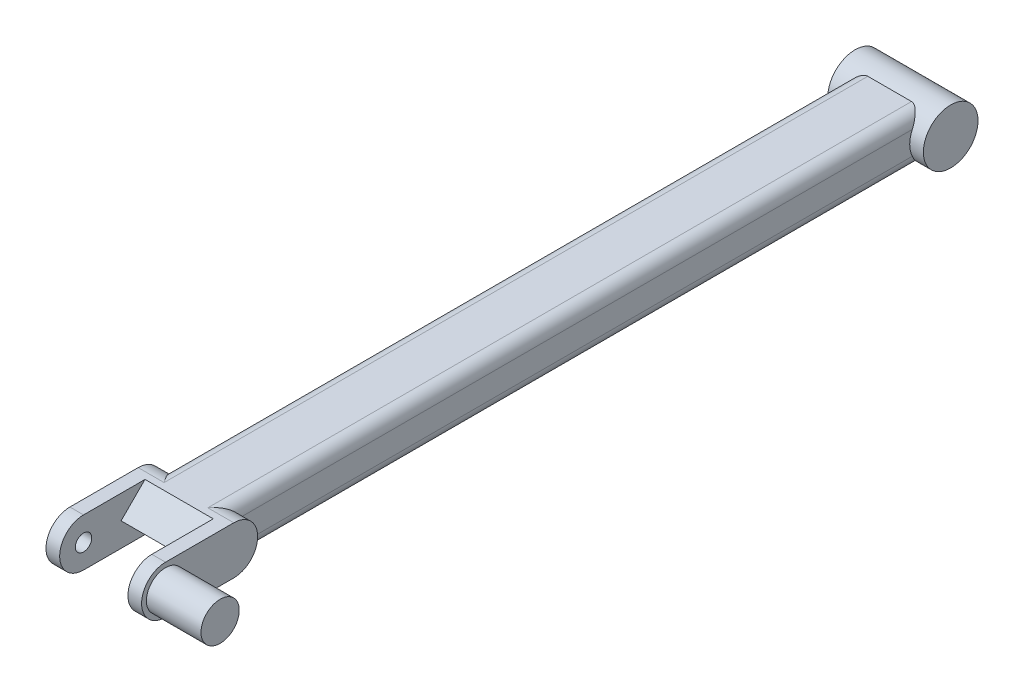
SolidWorks part; units mm, degrees
ref_plane "Ebene vorne" through (0, 0, 0) normal (0, 0, 1) x (1, 0, 0)
ref_plane "Ebene oben" through (0, 0, 0) normal (0, 1, 0) x (1, 0, 0)
ref_plane "Ebene rechts" through (0, 0, 0) normal (1, 0, 0) x (0, 0, -1)
sketch "Skizze1" plane through (0, 0, 0) normal (1, 0, 0) x (0, 0, -1)
  circle A0 centre (0, 0) radius 20
extrude "Aufsatz-Linear austragen1" add sketch "Skizze1" along normal blind 35 and the other way blind 35
sketch "Skizze2" plane through (0, 0, 0) normal (0, 0, 1) x (1, 0, 0)
  line L1 (-25, 17.5) -> (25, 17.5)
  line L2 (-25, 17.5) -> (-25, -17.5)
  line L3 (-25, -17.5) -> (25, -17.5)
  line L4 (25, 17.5) -> (25, -17.5)
  point P4 (-25, 0)
  point P6 (0, 17.5)
  dimension "D1" = 50
  dimension "D2" = 35
extrude "Aufsatz-Linear austragen2" add sketch "Skizze2" along normal blind 550
sketch "Skizze3" plane through (-25, 0, 0) normal (-1, 0, 0) x (0, 0, 1)
  line L0 (550, 17.5) -> (525, 17.5)
  line L1 (550, 17.5) -> (9.6825, 17.5) construction
  line L2 (550, -17.5) -> (525, -17.5)
  line L3 (550, -17.5) -> (9.6825, -17.5) construction
  line L4 (550, 17.5) -> (575, 17.5)
  line L5 (550, -17.5) -> (575, -17.5)
  arc A0 (525, 17.5) -> (525, -17.5) centre (525, 0) ccw
  arc A1 (575, 17.5) -> (575, -17.5) centre (575, 0) cw
  dimension "D1" = 25
  dimension "D2" = 25
extrude "Aufsatz-Linear austragen3" add sketch "Skizze3" along normal blind 10
sketch "Skizze4" plane through (-35, 0, 0) normal (-1, 0, 0) x (0, 0, 1)
  line L0 (575, 17.5) -> (525, 17.5) construction
  circle A0 centre (575, 0) radius 6
  point P4 (550, 17.5)
  dimension "D1" = 25
extrude "Schnitt-Linear austragen1" cut sketch "Skizze4" against normal up to next
mirror "Spiegeln1" about plane through (0, 0, 0) normal (1, 0, 0) of "Aufsatz-Linear austragen3", "Schnitt-Linear austragen1"
sketch "Skizze5" plane through (35, 0, 0) normal (1, 0, 0) x (0, 0, -1)
  circle A0 centre (-575, 0) radius 14
extrude "Aufsatz-Linear austragen4" add sketch "Skizze5" along normal blind 40
fillet "Verrundung1" radius 9 4 edges at (25, -17.5, 267.3412) (25, 17.5, 267.3412) (-25, -17.5, 267.3412) (-25, 17.5, 267.3412)
chamfer "Fase2" distance 20 distance2 20 2 edges at (0, -17.5, 550) (0, 17.5, 550)
